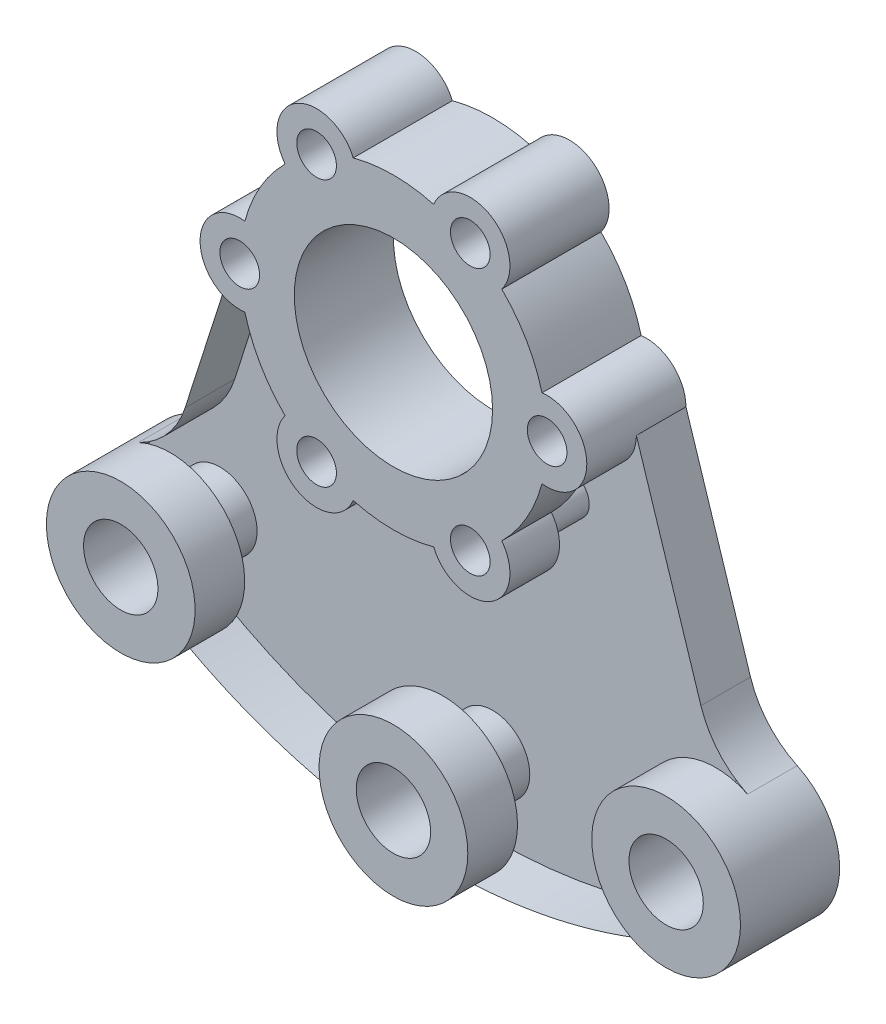
SolidWorks part; units mm, degrees
ref_plane "Alzado" through (0, 0, 0) normal (0, 0, 1) x (1, 0, 0)
ref_plane "Planta" through (0, 0, 0) normal (0, 1, 0) x (1, 0, 0)
ref_plane "Vista lateral" through (0, 0, 0) normal (1, 0, 0) x (0, 0, -1)
sketch "Croquis1" plane through (0, 0, 0) normal (0, 0, 1) x (1, 0, 0)
  line L0 (0, 46.9506) -> (0, -80) construction
  line L1 (-55.4441, 0) -> (60.703, 0) construction
  circle A0 centre (0, 0) radius 20
  circle A2 centre (31, 0) radius 4
  arc A3 (29.9677, -7.9331) -> (29.9677, 7.9331) centre (31, 0) ccw
  circle A4 centre (15.5, -26.8468) radius 4
  arc A5 (8.1136, -29.9194) -> (21.8542, -21.9863) centre (15.5, -26.8468) ccw
  circle A6 centre (-15.5, -26.8468) radius 4
  arc A7 (-21.8542, -21.9863) -> (-8.1136, -29.9194) centre (-15.5, -26.8468) ccw
  circle A8 centre (-31, 0) radius 4
  arc A9 (-29.9677, 7.9331) -> (-29.9677, -7.9331) centre (-31, 0) ccw
  circle A10 centre (-15.5, 26.8468) radius 4
  arc A11 (-8.1136, 29.9194) -> (-21.8542, 21.9863) centre (-15.5, 26.8468) ccw
  circle A12 centre (15.5, 26.8468) radius 4
  arc A13 (21.8542, 21.9863) -> (8.1136, 29.9194) centre (15.5, 26.8468) ccw
  arc A14 (-29.9677, -7.9331) -> (-21.8542, -21.9863) centre (0, 0) ccw
  arc A15 (-21.8542, 21.9863) -> (-29.9677, 7.9331) centre (0, 0) ccw
  arc A16 (8.1136, 29.9194) -> (-8.1136, 29.9194) centre (0, 0) ccw
  arc A17 (29.9677, 7.9331) -> (21.8542, 21.9863) centre (0, 0) ccw
  arc A18 (21.8542, -21.9863) -> (29.9677, -7.9331) centre (0, 0) ccw
  arc A19 (-8.1136, -29.9194) -> (8.1136, -29.9194) centre (0, 0) ccw
  circle A20 centre (0, -80) radius 7.5
  circle A21 centre (0, -80) radius 15
  circle A22 centre (55, -65) radius 7.5
  circle A23 centre (55, -65) radius 15
  circle A24 centre (-55, -65) radius 15
  circle A25 centre (-55, -65) radius 7.5
  point P29 (0, 0)
  dimension "D1" = 40
  dimension "D2" = 15
  dimension "D3" = 8
  dimension "D4" = 16
  dimension "D6" = 30
  dimension "D8" = 15
  dimension "D9" = 30
  dimension "D7" = 80
  dimension "D10" = 65
  dimension "D11" = 110
  dimension "D5" = 6
extrude "Saliente-Extruir1" add sketch "Croquis1" along normal blind 20
sketch "Croquis2" plane through (0, 0, 0) normal (0, 0, 1) x (1, 0, 0)
  line L0 (39, 0) -> (52.0172, -40.6787)
  line L1 (-39, 0) -> (-52.0172, -40.6787)
  line L2 (39, 0) -> (-39, 0)
  arc A0 (29.9677, -7.9331) -> (29.9677, 7.9331) centre (31, 0) ccw construction
  circle A1 centre (55, -65) radius 15 construction
  arc A2 (-29.9677, 7.9331) -> (-29.9677, -7.9331) centre (-31, 0) ccw construction
  circle A3 centre (-55, -65) radius 15 construction
  arc A4 (61.4367, -51.4513) -> (55, -80) centre (55, -65) cw
  arc A5 (-61.4367, -51.4513) -> (-55, -80) centre (-55, -65) ccw
  arc A6 (52.0172, -40.6787) -> (61.4367, -51.4513) centre (69.1608, -35.1928) ccw
  arc A7 (-52.0172, -40.6787) -> (-61.4367, -51.4513) centre (-69.1608, -35.1928) cw
  arc A8 (55, -80) -> (-55, -80) centre (0, 13.3333) cw
  point P20 (55, -50)
  point P23 (-55, -50)
  dimension "D1" = 18
extrude "Saliente-Extruir2" add sketch "Croquis2" along normal blind 10
sketch "Croquis5" plane through (0, 0, 10) normal (0, 0, 1) x (1, 0, 0)
  line L0 (-20, 0) -> (20, 0)
  arc A0 (-20, 0) -> (20, 0) centre (0, 0) ccw
extrude "Cortar-Extruir2" cut sketch "Croquis5" against normal blind 10
sketch "Croquis6" plane through (0, 0, 10) normal (0, 0, 1) x (1, 0, 0)
  line L0 (-35, 0) -> (-27, 0)
  line L1 (27, 0) -> (35, 0)
  circle A0 centre (-55, -65) radius 7.5
  circle A1 centre (0, -80) radius 7.5
  circle A2 centre (55, -65) radius 7.5
  circle A3 centre (15.5, -26.8468) radius 4
  circle A4 centre (-15.5, -26.8468) radius 4
  arc A5 (-35, 0) -> (-27, 0) centre (-31, 0) ccw
  arc A6 (27, 0) -> (35, 0) centre (31, 0) ccw
extrude "Cortar-Extruir3" cut sketch "Croquis6" against normal blind 10
